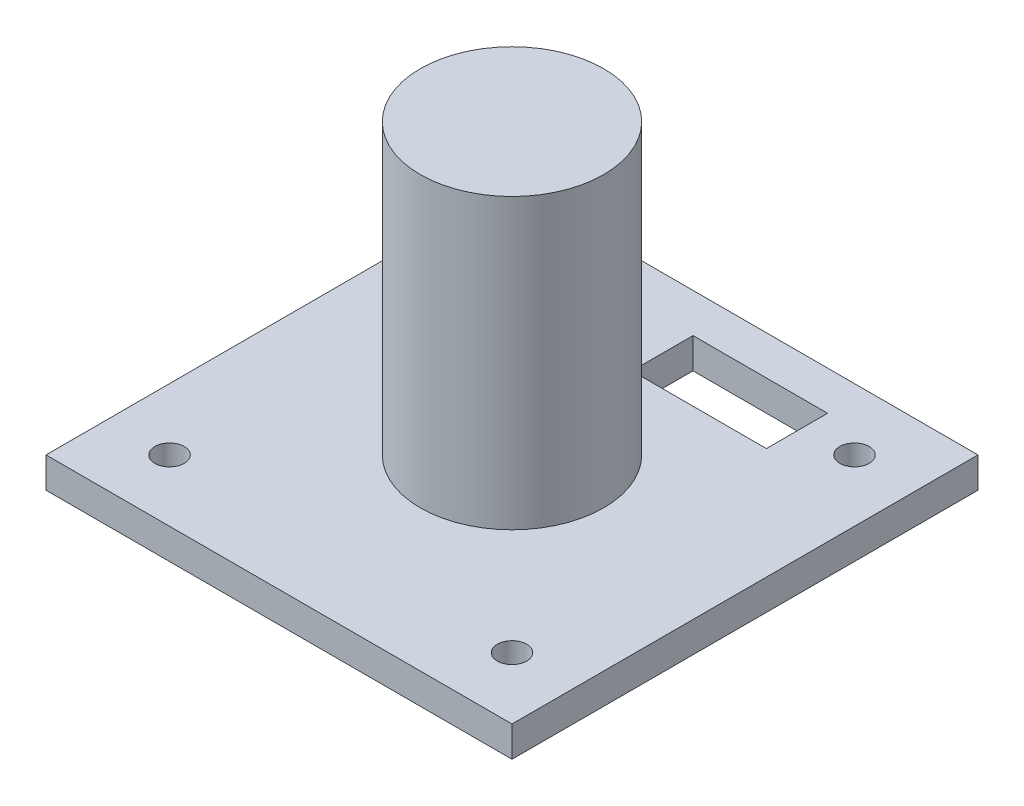
SolidWorks part; units mm, degrees
ref_plane "Front Plane" through (0, 0, 0) normal (0, 0, 1) x (1, 0, 0)
ref_plane "Top Plane" through (0, 0, 0) normal (0, 1, 0) x (1, 0, 0)
ref_plane "Right Plane" through (0, 0, 0) normal (1, 0, 0) x (0, 0, -1)
sketch "Sketch1" plane through (0, 0, 0) normal (0, 1, 0) x (1, 0, 0)
  line L0 (-19.05, 19.05) -> (-19.05, -19.05)
  line L1 (-19.05, -19.05) -> (19.05, -19.05)
  line L2 (19.05, -19.05) -> (19.05, 19.05)
  line L3 (19.05, 19.05) -> (-19.05, 19.05)
  line L4 (-1.05, 15.85) -> (9.95, 15.85)
  line L5 (9.95, 15.85) -> (9.95, 10.85)
  line L6 (9.95, 10.85) -> (-1.05, 10.85)
  line L7 (-1.05, 10.85) -> (-1.05, 15.85)
  circle A0 centre (0, 0) radius 7.5
  circle A1 centre (-14, 14) radius 1.2
  circle A2 centre (14, 14) radius 1.2
  circle A3 centre (14, -14) radius 1.2
  circle A4 centre (-14, -14) radius 1.2
  point P19 (0, 0)
  point P20 (0, 19.05)
  point P21 (-14, 14)
  point P22 (14, 14)
  point P23 (14, -14)
  point P24 (-14, -14)
  point P25 (0, 0)
  point P26 (0, 0)
  dimension "D2" = 38.1
  dimension "D3" = 28
  dimension "D4" = 15
  dimension "D5" = 2.4
  dimension "D8" = 28
  dimension "D6" = 11
  dimension "D7" = 29
  dimension "D9" = 14
  dimension "D10" = 5
  dimension "D11" = 19.05
  dimension "D12" = 14
  dimension "D13" = 3.2
extrude "Boss-Extrude1" add sketch "Sketch1" along normal blind 2.5 contours L2 L3 L0 L1 A4 A3 A2 A1 A0 L6 L7 L4 L5 region at (0, 0, -18.5112)
extrude "Boss-Extrude2" add sketch "Sketch1<6>" along normal blind 26.1 contours A0 region at (0, 0, 0)
sketch "Sketch1<6>" plane through (0, 0, 0) normal (0, 1, 0) x (1, 0, 0) same geometry as "Sketch1"
